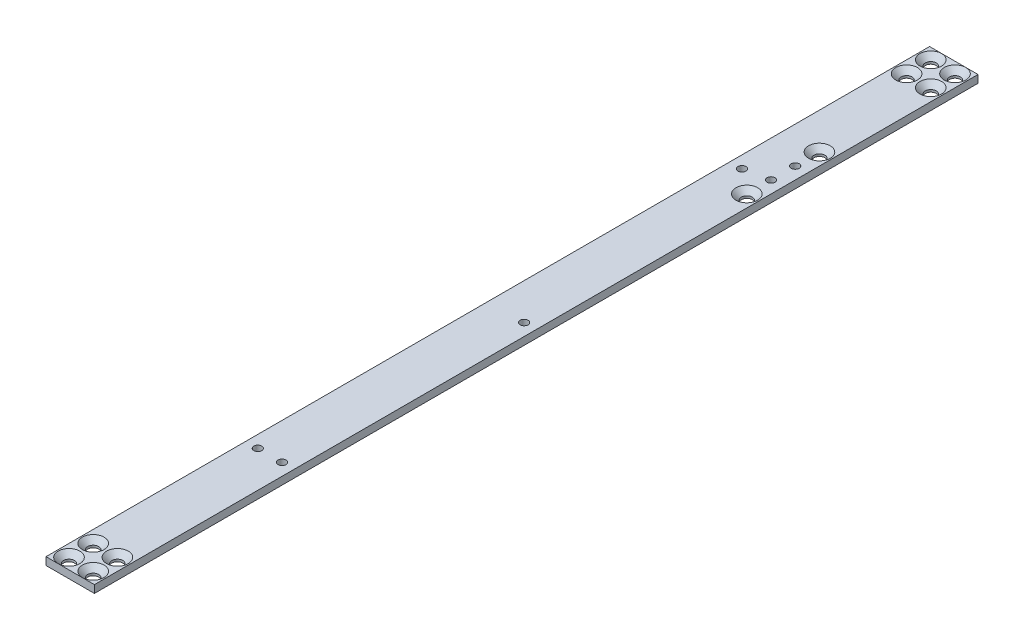
SolidWorks part; units mm, degrees
ref_plane "Front Plane" through (0, 0, 0) normal (0, 0, 1) x (1, 0, 0)
ref_plane "Top Plane" through (0, 0, 0) normal (0, 1, 0) x (1, 0, 0)
ref_plane "Right Plane" through (0, 0, 0) normal (1, 0, 0) x (0, 0, -1)
sketch "Sketch1" plane through (0, 0, 0) normal (0, 1, 0) x (1, 0, 0)
  line L1 (-10, -182.5) -> (10, -182.5)
  line L2 (-10, -182.5) -> (-10, 182.5)
  line L3 (-10, 182.5) -> (10, 182.5)
  line L4 (10, -182.5) -> (10, 182.5)
  line L5 (-10, -182.5) -> (10, 182.5) construction
  line L6 (-10, 182.5) -> (10, -182.5) construction
  point P1 (0, 0)
  dimension "D1" = 365
  dimension "D2" = 20
extrude "Boss-Extrude1" add sketch "Sketch1" along normal blind 3.175
hole_wizard "CSK for M4 SFHCS1" positions "Sketch2" profile "Sketch3" countersink size "M4" standard "ANSI Metric" end condition through all
sketch "Sketch2" plane through (0, 3.175, 0) normal (0, 1, 0) x (1, 0, 0)
  line L1 (-5, -178) -> (5, -178)
  line L2 (-5, -178) -> (-5, -168)
  line L3 (-5, -168) -> (5, -168)
  line L4 (5, -178) -> (5, -168)
  line L5 (-5, -178) -> (5, -168) construction
  line L6 (-5, -168) -> (5, -178) construction
  line L7 (-10, -182.5) -> (10, -182.5) construction
  line L8 (-10, 182.5) -> (-10, -182.5) construction
  line L9 (-55, 0) -> (55, 0) construction
  line L10 (-5, 168) -> (5, 178) construction
  line L11 (-5, 178) -> (5, 168) construction
  line L12 (5, 178) -> (5, 168)
  line L13 (-5, 168) -> (5, 168)
  line L14 (-5, 178) -> (-5, 168)
  line L15 (-5, 178) -> (5, 178)
  line L16 (5, 92) -> (5, 122)
  line L18 (10, 182.5) -> (-10, 182.5) construction
  point P2 (5, -168)
  point P37 (-5, -178)
  point P38 (-5, -168)
  point P39 (5, -178)
  point P45 (0, -173)
  point P54 (5, 178)
  point P55 (-5, 168)
  point P56 (-5, 178)
  point P57 (5, 168)
  point P58 (5, 92)
  point P59 (5, 122)
  point P62 (5, 107)
  dimension "D1" = 10
  dimension "D2" = 4.5
  dimension "D3" = 10
  dimension "D4" = 75.5
  dimension "D5" = 30
sketch "Sketch3" plane through (5, 3.175, 168) normal (1, 0, 0) x (0, 0, 1)
  line L0 (0, 0) -> (0, 3.175)
  line L1 (0, 3.175) -> (2.25, 3.175)
  line L2 (2.25, 3.175) -> (2.25, 2.23)
  line L3 (2.25, 2.23) -> (4.48, 0)
  line L5 (4.48, 0) -> (0, 0)
  line L6 (-2.25, 2.23) -> (-4.48, 0) construction
  line L11 (0, -6.35) -> (0, 107.95) construction
  dimension "Thru Hole Dia." = 4.5
  dimension "Thru Hole Depth" = 3.175
  dimension "Near C'Sink Dia." = 8.96
  dimension "Near C'Sink Angle" = 90
hole_wizard "M4x0.7 Tapped Hole1" positions "Sketch4" profile "Sketch6" tap size "M4x0.7" standard "ANSI Metric" end condition through all
sketch "Sketch4" plane through (0, 3.175, 0) normal (0, 1, 0) x (1, 0, 0)
  line L0 (-5, -100) -> (-5, 100)
  line L2 (-10, 182.5) -> (-10, -182.5) construction
  line L3 (0, -55) -> (0, 55) construction
  line L5 (5, -100) -> (5, 0)
  line L6 (5, 102) -> (5, 112)
  line L8 (10, 182.5) -> (-10, 182.5) construction
  point P1 (-5, -100)
  point P2 (-5, 100)
  point P6 (-5, 0)
  point P19 (5, -100)
  point P24 (5, 0)
  point P29 (5, 102)
  point P30 (5, 112)
  point P33 (5, 107)
  dimension "D1" = 200
  dimension "D2" = 5
  dimension "D3" = 100
  dimension "D4" = 10
  dimension "D5" = 75.5
sketch "Sketch6" plane through (-5, 3.175, 100) normal (1, 0, 0) x (0, 0, 1)
  line L0 (0, 0) -> (0, 3.175)
  line L1 (0, 3.175) -> (1.65, 3.175)
  line L2 (1.65, 3.175) -> (1.65, 0)
  line L5 (1.65, 0) -> (0, 0)
  line L11 (0, -6.35) -> (0, 107.95) construction
  dimension "Thru Tap Drill Dia." = 3.3
  dimension "Thru Tap Drill Depth" = 3.175
cosmetic thread "Hole Thread1"
cosmetic thread "Hole Thread2"
cosmetic thread "Hole Thread3"
cosmetic thread "Hole Thread4"
cosmetic thread "Hole Thread5"
cosmetic thread "Hole Thread6"
